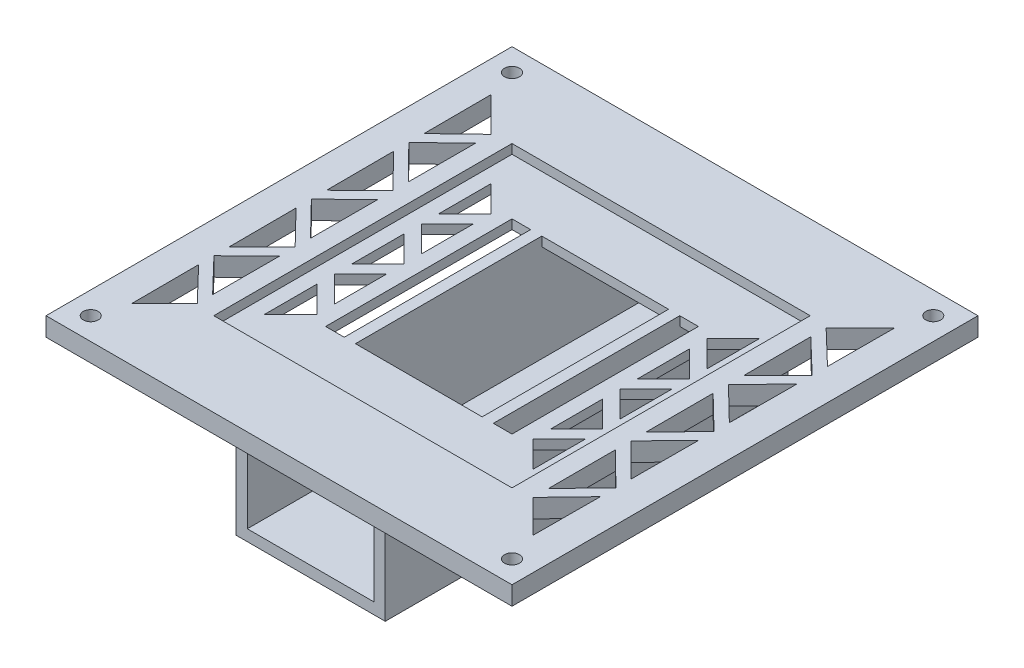
SolidWorks part; units mm, degrees
other "마크업1"
sketch "스케치10" plane through (-62.5, -31.5, -62.5) normal (-0.0294, -0.9842, -0.1746) x (0.6542, 0.1131, -0.7478)
ref_plane "정면" through (0, 0, 0) normal (0, 0, 1) x (1, 0, 0)
ref_plane "윗면" through (0, 0, 0) normal (0, 1, 0) x (1, 0, 0)
ref_plane "우측면" through (0, 0, 0) normal (1, 0, 0) x (0, 0, -1)
ref_axis "기준축1" through (0, 4.2, 0) along (0, -1, 0)
sketch "스케치2" plane through (0, 0, 0) normal (0, 1, 0) x (1, 0, 0)
  line L1 (62.5, 62.5) -> (-62.5, 62.5)
  line L2 (62.5, 62.5) -> (62.5, -62.5)
  line L3 (62.5, -62.5) -> (-62.5, -62.5)
  line L4 (-62.5, 62.5) -> (-62.5, -62.5)
  line L5 (62.5, 62.5) -> (-62.5, -62.5) construction
  line L6 (62.5, -62.5) -> (-62.5, 62.5) construction
  line L7 (-25, 25) -> (25, 25)
  line L8 (-25, 25) -> (-25, -25)
  line L9 (-25, -25) -> (25, -25)
  line L10 (25, 25) -> (25, -25)
  line L11 (-25, 25) -> (25, -25) construction
  line L12 (-25, -25) -> (25, 25) construction
  circle A0 centre (-56.5, 56.5) radius 2
  circle A1 centre (56.5, 56.5) radius 2
  circle A2 centre (-56.5, -56.5) radius 2
  circle A3 centre (56.5, -56.5) radius 2
  point P0 (0, 0)
  point P6 (0, 0)
  dimension "D5" = 4
  dimension "D1" = 125
  dimension "D2" = 125
  dimension "D3" = 50
  dimension "D4" = 50
  dimension "D6" = 6
  dimension "D7" = 6
  dimension "D8" = 6
  dimension "D9" = 6
extrude "보스-돌출1" add sketch "스케치2" along normal mid plane 5
sketch "스케치6" plane through (0, 0, 0) normal (0, 0, 1) x (1, 0, 0)
  line L0 (0, 0) -> (50000, 0) construction
  line L2 (0, 0) -> (0, -50000) construction
  line L3 (-20, 0) -> (-20, -31.5)
  line L4 (-20, -31.5) -> (20, -31.5)
  line L6 (17, -28.5) -> (-17, -28.5)
  line L7 (-17, -28.5) -> (-17, 0)
  line L8 (-17, 0) -> (-20, 0)
  line L9 (17, 0) -> (20, 0)
  line L10 (17, -28.5) -> (17, 0)
  line L11 (20, 0) -> (20, -31.5)
  line L12 (-62.5, -2.5) -> (62.5, -2.5) construction
  point P14 (0, -28.5)
  point P15 (0, -31.5)
  dimension "D1" = 34
  dimension "D2" = 3
  dimension "D3" = 26
  dimension "D4" = 3
extrude "보스-돌출4" add sketch "스케치6" along normal mid plane 108
sketch "스케치7" plane through (0, 0, 0) normal (0, 1, 0) x (1, 0, 0)
  line L1 (-40, 40) -> (40, 40)
  line L2 (-40, 40) -> (-40, -40)
  line L3 (-40, -40) -> (40, -40)
  line L4 (40, 40) -> (40, -40)
  line L5 (-40, 40) -> (40, -40) construction
  line L6 (-40, -40) -> (40, 40) construction
  point P0 (0, 0)
  dimension "D1" = 80
  dimension "D2" = 80
extrude "컷-돌출1" cut sketch "스케치7" along normal blind 10
sketch "스케치8" plane through (0, 2.5, 0) normal (0, 1, 0) x (1, 0, 0)
  line L14 (54.1085, 30.5155) -> (54.094, 26.4186) construction
  line L15 (54.0793, 22.2856) -> (54.0155, 4.2857)
  line L20 (44.9633, 35.1872) -> (44.959, 39.3022) construction
  line L21 (36, -30.3431) -> (36, -16.3431)
  line L22 (29, -23.3431) -> (36, -30.3431)
  line L23 (29, 18.6716) -> (29, 4.6716)
  line L24 (36, 30.3431) -> (29, 23.3431)
  line L41 (53.8296, -48.1728) -> (45.0411, -39.3843)
  line L42 (45.0368, -35.2728) -> (45.018, -17.2728)
  line L43 (44.959, 39.3022) -> (54.1723, 48.5154)
  line L44 (54.1723, 48.5154) -> (54.1085, 30.5155)
  line L83 (62.5, -62.5) -> (-62.5, 62.5) construction
  line L94 (62.5, 62.5) -> (-62.5, -62.5) construction
  line L96 (45.0411, -39.3843) -> (53.8934, -30.1704)
  line L97 (45.0368, -35.2728) -> (53.9081, -26.0392)
  line L98 (53.9081, -26.0392) -> (45.018, -17.2728)
  line L100 (53.9226, -21.9404) -> (45.0138, -13.1555)
  line L101 (45.0138, -13.1555) -> (53.9864, -3.9443)
  line L103 (45.0095, -9.0428) -> (54.001, 0.1878)
  line L104 (54.001, 0.1878) -> (44.9907, 8.9572)
  line L106 (44.9864, 13.0733) -> (54.0155, 4.2857)
  line L107 (44.9864, 13.0733) -> (54.0793, 22.2856)
  line L108 (44.9821, 17.1872) -> (54.094, 26.4186)
  line L110 (54.094, 26.4186) -> (44.9633, 35.1872)
  line L112 (54.1085, 30.5155) -> (44.959, 39.3022)
  line L113 (44.9864, 13.0733) -> (44.9821, 17.1872) construction
  line L114 (44.9821, 17.1872) -> (44.9633, 35.1872)
  line L115 (54.094, 26.4186) -> (54.0793, 22.2856) construction
  line L116 (44.9907, 8.9572) -> (44.9864, 13.0733) construction
  line L117 (54.001, 0.1878) -> (53.9864, -3.9443) construction
  line L118 (53.9864, -3.9443) -> (53.9226, -21.9404)
  line L119 (54.0155, 4.2857) -> (54.001, 0.1878) construction
  line L120 (45.0138, -13.1555) -> (45.0095, -9.0428) construction
  line L121 (45.0095, -9.0428) -> (44.9907, 8.9572)
  line L122 (45.0411, -39.3843) -> (45.0368, -35.2728) construction
  line L123 (53.9081, -26.0392) -> (53.8934, -30.1704) construction
  line L124 (53.8934, -30.1704) -> (53.8296, -48.1728)
  line L125 (53.9226, -21.9404) -> (53.9081, -26.0392) construction
  line L126 (45.018, -17.2728) -> (45.0138, -13.1555) construction
  line L127 (29, 23.3431) -> (36, 16.3431)
  line L128 (29, 18.6716) -> (36, 11.6716)
  line L129 (36, 11.6716) -> (29, 4.6716)
  line L130 (29, 0) -> (36, 7)
  line L131 (29, 0) -> (36, -7)
  line L132 (36, -11.6716) -> (29, -4.6716)
  line L133 (36, -11.6716) -> (29, -18.6716)
  line L134 (36, -16.3431) -> (29, -23.3431)
  line L135 (29, 23.3431) -> (29, 18.6716) construction
  line L136 (36, 11.6716) -> (36, 16.3431) construction
  line L137 (36, 16.3431) -> (36, 30.3431)
  line L138 (36, 7) -> (36, 11.6716) construction
  line L139 (29, 4.6716) -> (29, 0) construction
  line L140 (29, -4.6716) -> (29, -18.6716)
  line L141 (29, 0) -> (29, -4.6716) construction
  line L142 (36, -11.6716) -> (36, -7) construction
  line L143 (36, -7) -> (36, 7)
  line L144 (29, -18.6716) -> (29, -23.3431) construction
  line L145 (36, -16.3431) -> (36, -11.6716) construction
  line L146 (0, -18.7) -> (0, 18.7) construction
  line L147 (-36, -16.3431) -> (-36, -11.6716) construction
  line L148 (-29, -18.6716) -> (-29, -23.3431) construction
  line L149 (-36, -11.6716) -> (-36, -7) construction
  line L150 (-29, 0) -> (-29, -4.6716) construction
  line L151 (-29, 4.6716) -> (-29, 0) construction
  line L152 (-36, 7) -> (-36, 11.6716) construction
  line L153 (-36, 11.6716) -> (-36, 16.3431) construction
  line L154 (-29, 23.3431) -> (-29, 18.6716) construction
  line L155 (-45.018, -17.2728) -> (-45.0138, -13.1555) construction
  line L156 (-53.9226, -21.9404) -> (-53.9081, -26.0392) construction
  line L157 (-53.9081, -26.0392) -> (-53.8934, -30.1704) construction
  line L158 (-45.0411, -39.3843) -> (-45.0368, -35.2728) construction
  line L159 (-45.0138, -13.1555) -> (-45.0095, -9.0428) construction
  line L160 (-54.0155, 4.2857) -> (-54.001, 0.1878) construction
  line L161 (-54.001, 0.1878) -> (-53.9864, -3.9443) construction
  line L162 (-44.9907, 8.9572) -> (-44.9864, 13.0733) construction
  line L163 (-54.094, 26.4186) -> (-54.0793, 22.2856) construction
  line L164 (-44.9864, 13.0733) -> (-44.9821, 17.1872) construction
  line L165 (-44.9633, 35.1872) -> (-44.959, 39.3022) construction
  line L166 (-54.1085, 30.5155) -> (-54.094, 26.4186) construction
  line L167 (-36, -7) -> (-36, 7)
  line L168 (-29, -4.6716) -> (-29, -18.6716)
  line L169 (-36, 16.3431) -> (-36, 30.3431)
  line L170 (-36, -16.3431) -> (-29, -23.3431)
  line L171 (-36, -11.6716) -> (-29, -18.6716)
  line L172 (-36, -11.6716) -> (-29, -4.6716)
  line L173 (-29, 0) -> (-36, -7)
  line L174 (-29, 0) -> (-36, 7)
  line L175 (-36, 11.6716) -> (-29, 4.6716)
  line L176 (-29, 18.6716) -> (-36, 11.6716)
  line L177 (-29, 23.3431) -> (-36, 16.3431)
  line L178 (-53.8934, -30.1704) -> (-53.8296, -48.1728)
  line L179 (-45.0095, -9.0428) -> (-44.9907, 8.9572)
  line L180 (-53.9864, -3.9443) -> (-53.9226, -21.9404)
  line L181 (-44.9821, 17.1872) -> (-44.9633, 35.1872)
  line L182 (-54.1085, 30.5155) -> (-44.959, 39.3022)
  line L183 (-54.094, 26.4186) -> (-44.9633, 35.1872)
  line L184 (-44.9821, 17.1872) -> (-54.094, 26.4186)
  line L185 (-44.9864, 13.0733) -> (-54.0793, 22.2856)
  line L186 (-44.9864, 13.0733) -> (-54.0155, 4.2857)
  line L187 (-54.001, 0.1878) -> (-44.9907, 8.9572)
  line L188 (-45.0095, -9.0428) -> (-54.001, 0.1878)
  line L189 (-45.0138, -13.1555) -> (-53.9864, -3.9443)
  line L190 (-53.9226, -21.9404) -> (-45.0138, -13.1555)
  line L191 (-53.9081, -26.0392) -> (-45.018, -17.2728)
  line L192 (-45.0368, -35.2728) -> (-53.9081, -26.0392)
  line L193 (-45.0411, -39.3843) -> (-53.8934, -30.1704)
  line L194 (-54.1723, 48.5154) -> (-54.1085, 30.5155)
  line L195 (-44.959, 39.3022) -> (-54.1723, 48.5154)
  line L196 (-45.0368, -35.2728) -> (-45.018, -17.2728)
  line L197 (-53.8296, -48.1728) -> (-45.0411, -39.3843)
  line L198 (-36, 30.3431) -> (-29, 23.3431)
  line L199 (-29, 18.6716) -> (-29, 4.6716)
  line L200 (-29, -23.3431) -> (-36, -30.3431)
  line L201 (-36, -30.3431) -> (-36, -16.3431)
  line L202 (-54.0793, 22.2856) -> (-54.0155, 4.2857)
  dimension "D1" = 29
  dimension "D2" = 36
  dimension "D3" = 45
  dimension "D4" = 54
  dimension "D5" = 4
  dimension "D6" = 4
  dimension "D8" = 14
  dimension "D9" = 8.23
  dimension "D10" = 4.115
  dimension "D11" = 18
  dimension "D7" = 18
  dimension "D12" = 14
  dimension "D13" = 8.23
  dimension "D14" = 18
  dimension "D16" = 8.23
  dimension "D17" = 18
  dimension "D19" = 8.23
  dimension "D20" = 8.23
  dimension "D21" = 17.9963
  dimension "D22" = 18
  dimension "D23" = 18.0024
  dimension "D24" = 14
  dimension "D25" = 14
extrude "컷-돌출2" cut sketch "스케치8" against normal blind 5 and the other way through all
pattern_circular "원형 패턴1" [suppressed] count 4 over 360 about axis through (0, 4.2, 0) along (0, -1, 0) of bodies 108
